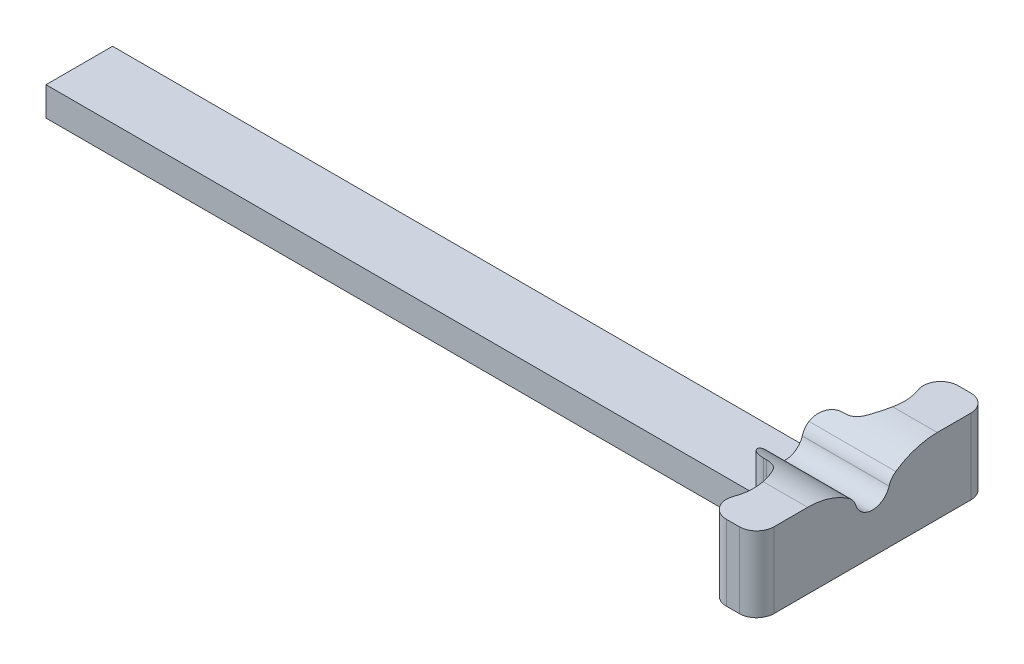
SolidWorks part; units mm, degrees
note: The reader was unsure of these and kept them because the rebuilt part matched: shared geometry of "草图1<3>".
ref_plane "前视基准面" through (0, 0, 0) normal (0, 0, 1) x (1, 0, 0)
ref_plane "上视基准面" through (0, 0, 0) normal (0, 1, 0) x (1, 0, 0)
ref_plane "右视基准面" through (0, 0, 0) normal (1, 0, 0) x (0, 0, -1)
other "图形1"
sketch "草图1" plane through (0, 0, 0) normal (0, 1, 0) x (1, 0, 0)
  line L0 (0, 0) -> (137, 0) construction
  line L1 (137, -17) -> (137, 17)
  line L2 (134, 20) -> (131.7819, 20)
  line L3 (125.5, 6.8377) -> (125, 6.8377)
  line L4 (122, 3.8377) -> (122, -3.8377)
  line L5 (0, -5.75) -> (0, 5.75)
  line L6 (0, 5.75) -> (122.6885, 5.75)
  line L7 (0, -5.75) -> (122.6885, -5.75)
  line L8 (125.5, -6.8377) -> (125, -6.8377)
  line L9 (134, -20) -> (131.7819, -20)
  arc A0 (128.9693, 15.9565) -> (127.9545, 8.1128) centre (121, 13) cw
  arc A1 (137, 17) -> (134, 20) centre (134, 17) ccw
  arc A2 (131.7819, 20) -> (128.9693, 15.9565) centre (131.7819, 17) ccw
  arc A3 (125, 6.8377) -> (122, 3.8377) centre (125, 3.8377) ccw
  arc A4 (127.9545, 8.1128) -> (125.5, 6.8377) centre (125.5, 9.8377) cw
  arc A5 (127.9545, -8.1128) -> (125.5, -6.8377) centre (125.5, -9.8377) ccw
  arc A6 (125, -6.8377) -> (122, -3.8377) centre (125, -3.8377) cw
  arc A7 (131.7819, -20) -> (128.9693, -15.9565) centre (131.7819, -17) cw
  arc A8 (137, -17) -> (134, -20) centre (134, -17) cw
  arc A9 (128.9693, -15.9565) -> (127.9545, -8.1128) centre (121, -13) ccw
  point P34 (122, 0)
  dimension "D3" = 8.5
  dimension "D6" = 3
  dimension "D4" = 26
  dimension "D7" = 11.5
  dimension "D1" = 137
  dimension "D2" = 40
  dimension "D5" = 16
  dimension "D8" = 122
  dimension "D9" = 11.5
extrude "凸台-拉伸1" add sketch "草图1" along normal blind 13 contours L0 L4 A6 L8 A5 A9 A7 L9 A8 L1 | L4 L0 L1 A1 L2 A2 A0 A4 L3 A3
extrude "凸台-拉伸2" add sketch "草图1<3>" along normal blind 5 contours L5 L0 L4 A3 L6 | L0 L5 L7 A6 L4
sketch "草图1<3>" plane through (0, 0, 0) normal (0, 1, 0) x (1, 0, 0) same geometry as "草图1"
sketch "草图2" plane through (137, 0, 0) normal (1, 0, 0) x (0, 0, -1)
  line L0 (0, 0.1492) -> (0, 13) construction
  line L1 (-17, 13) -> (17, 13) construction
  line L2 (-17, 0) -> (17, 0) construction
  line L3 (-11.1931, 13) -> (11.1931, 13)
  arc A0 (-2.875, 9.143) -> (2.875, 9.143) centre (0, 10) ccw
  arc A1 (-2.875, 9.143) -> (-4.0311, 10.7449) centre (-5.75, 8.2861) ccw
  arc A2 (-4.0311, 10.7449) -> (-11.1931, 13) centre (-11.1931, 0.5) ccw
  arc A3 (4.0311, 10.7449) -> (11.1931, 13) centre (11.1931, 0.5) cw
  arc A4 (2.875, 9.143) -> (4.0311, 10.7449) centre (5.75, 8.2861) cw
  dimension "D1" = 6
  dimension "D3" = 3
  dimension "D5" = 12.5
  dimension "D2" = 10
  dimension "D4" = 11.5
extrude "切除-拉伸1" cut sketch "草图2" against normal through all
